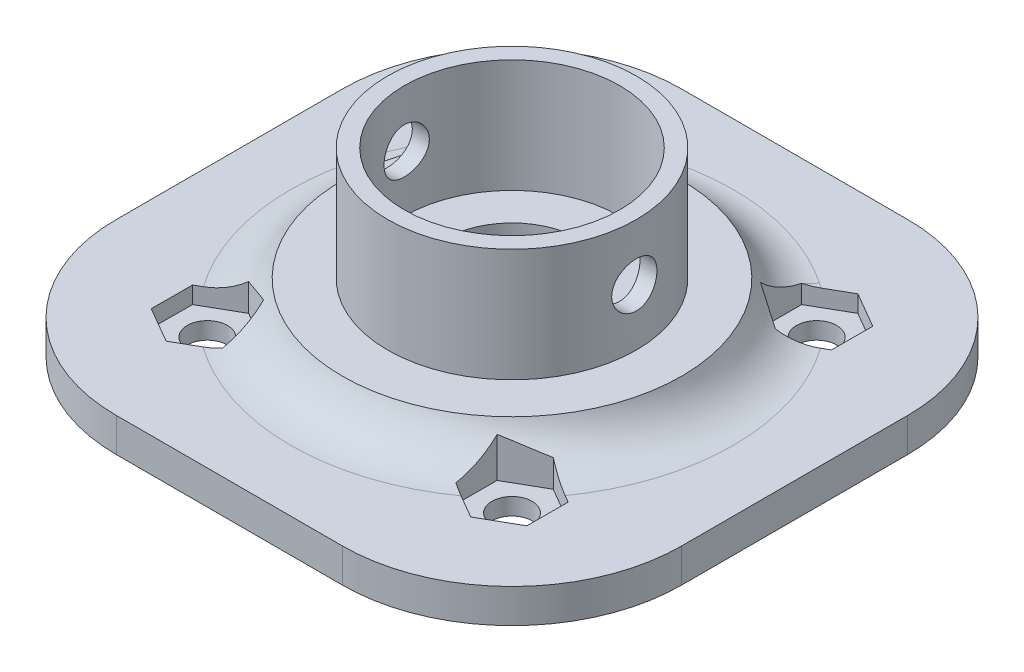
SolidWorks part; units mm, degrees
ref_plane "Front Plane" through (0, 0, 0) normal (0, 0, 1) x (1, 0, 0)
ref_plane "Top Plane" through (0, 0, 0) normal (0, 1, 0) x (1, 0, 0)
ref_plane "Right Plane" through (0, 0, 0) normal (1, 0, 0) x (0, 0, -1)
sketch "Sketch1" plane through (0, 0, 0) normal (0, 1, 0) x (1, 0, 0)
  line L1 (0, 0) -> (50, 0)
  line L2 (0, 0) -> (0, 50)
  line L3 (0, 50) -> (50, 50)
  line L4 (50, 0) -> (50, 50)
  dimension "D1" = 50
  dimension "D2" = 50
extrude "Boss-Extrude1" add sketch "Sketch1" along normal blind 3
sketch "Sketch2" plane through (0, 3, 0) normal (0, 1, 0) x (1, 0, 0)
  line L2 (50, 0) -> (50, 50) construction
  line L3 (0, 0) -> (50, 0) construction
  circle A0 centre (11.53, 38.47) radius 1.78
  circle A1 centre (38.47, 38.47) radius 1.78
  circle A2 centre (38.47, 11.53) radius 1.78
  circle A3 centre (11.53, 11.53) radius 1.78
  circle A8 centre (25, 25) radius 10.1396
  dimension "D1" = 3.56
  dimension "D4" = 13.47
  dimension "D5" = 13.47
  dimension "D11" = 25
  dimension "D12" = 25
  dimension "D2" = 2
  dimension "D3" = 2
extrude "Cut-Extrude1" cut sketch "Sketch2" against normal blind 12
sketch "Sketch3" plane through (0, 3, 0) normal (0, 1, 0) x (1, 0, 0)
  line L0 (50, 50) -> (0, 50) construction
  line L1 (50, 0) -> (50, 50) construction
  circle A0 centre (25, 25) radius 15
  point P2 (25, 50)
  dimension "D1" = 25
  dimension "D2" = 25
  dimension "D3" = 30
extrude "Boss-Extrude3" add sketch "Sketch3" along normal blind 3
sketch "Sketch6" plane through (0, 6, 0) normal (0, 1, 0) x (1, 0, 0)
  line L0 (50, 0) -> (50, 50) construction
  line L1 (50, 50) -> (0, 50) construction
  circle A0 centre (25, 25) radius 11
  circle A1 centre (25, 25) radius 9.525
  dimension "D1" = 25
  dimension "D2" = 25
  dimension "D3" = 22
  dimension "D4" = 19.05
extrude "Boss-Extrude4" add sketch "Sketch6" along normal blind 10
fillet "Fillet2" radius 5 1 edges at (25, 3, -40)
fillet "Fillet3" radius 15 4 edges at (0, 1.5, 0) (50, 1.5, 0) (50, 1.5, -50) (0, 1.5, -50)
sketch "Sketch7" plane through (0, 0, 0) normal (-1, 0, 0) x (0, 0, 1)
  line L2 (-35, 3) -> (-15, 3) construction
  line L3 (-35, 3) -> (-35, 0) construction
  circle A1 centre (-25, 11) radius 2
  point P2 (-35, 1.5)
  dimension "D1" = 10
  dimension "D3" = 8
  dimension "D4" = 4
extrude "Cut-Extrude3" cut sketch "Sketch7" against normal blind 47
sketch "Sketch9" plane through (0, 3, 0) normal (0, -1, 0) x (1, 0, 0)
  circle A0 centre (25, -25) radius 10.1396
extrude "Cut-Extrude4" cut sketch "Sketch9" against normal blind 1.2
sketch "Sketch14" plane through (0, 3, 0) normal (0, 1, 0) x (1, 0, 0)
  line L0 (8.3857, 13.3585) -> (8.3743, 9.7212)
  line L1 (38.4586, 7.8927) -> (41.6143, 9.7015)
  line L2 (41.6143, 9.7015) -> (41.6257, 13.3388)
  line L3 (41.6257, 13.3388) -> (38.4814, 15.1673)
  line L4 (38.4814, 15.1673) -> (35.3257, 13.3585)
  line L5 (35.3257, 13.3585) -> (35.3143, 9.7212)
  line L6 (35.3143, 9.7212) -> (38.4586, 7.8927)
  line L7 (8.3743, 9.7212) -> (11.5186, 7.8927)
  line L8 (11.5186, 7.8927) -> (14.6743, 9.7015)
  line L9 (14.6743, 9.7015) -> (14.6857, 13.3388)
  line L10 (14.6857, 13.3388) -> (11.5414, 15.1673)
  line L11 (11.5414, 15.1673) -> (8.3857, 13.3585)
  line L12 (8.3857, 40.2985) -> (8.3743, 36.6612)
  line L13 (8.3743, 36.6612) -> (11.5186, 34.8327)
  line L14 (11.5186, 34.8327) -> (14.6743, 36.6415)
  line L15 (14.6743, 36.6415) -> (14.6857, 40.2788)
  line L16 (14.6857, 40.2788) -> (11.5414, 42.1073)
  line L17 (11.5414, 42.1073) -> (8.3857, 40.2985)
  line L18 (35.3257, 40.2985) -> (35.3143, 36.6612)
  line L19 (35.3143, 36.6612) -> (38.4586, 34.8327)
  line L20 (38.4586, 34.8327) -> (41.6143, 36.6415)
  line L21 (41.6143, 36.6415) -> (41.6257, 40.2788)
  line L22 (41.6257, 40.2788) -> (38.4814, 42.1073)
  line L23 (38.4814, 42.1073) -> (35.3257, 40.2985)
  circle A0 centre (38.47, 11.53) radius 3.15 construction
  circle A1 centre (11.53, 11.53) radius 3.15 construction
  circle A2 centre (11.53, 38.47) radius 3.15 construction
  circle A3 centre (38.47, 38.47) radius 3.15 construction
  point P1 (8.38, 11.5398)
  dimension "D3" = 6.3
  dimension "D1" = 2
  dimension "D2" = 2
extrude "Cut-Extrude5" cut sketch "Sketch14" against normal blind 1.5 and the other way through all
sketch "Sketch15" plane through (0, 6, 0) normal (0, 1, 0) x (1, 0, 0)
  circle A0 centre (25, 25) radius 6
  circle A1 centre (25, 25) radius 9.525 construction
  dimension "D1" = 12
  dimension "D2" = 0
extrude "Cut-Extrude6" cut sketch "Sketch15" against normal blind 10
